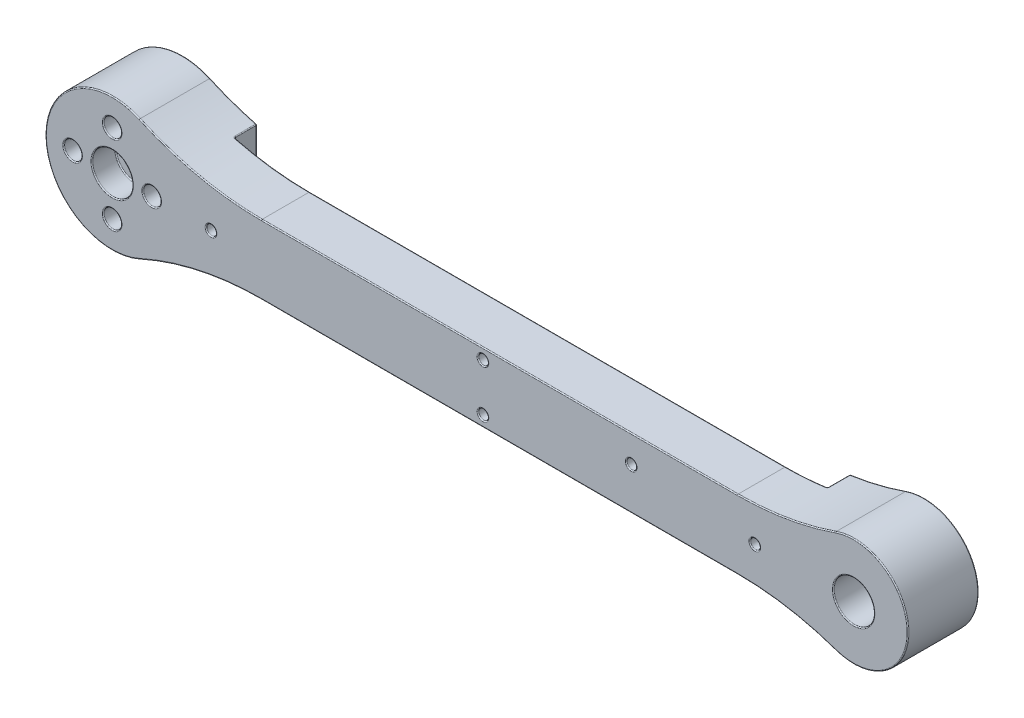
SolidWorks part; units mm, degrees
ref_plane "정면" through (0, 0, 0) normal (0, 0, 1) x (1, 0, 0)
ref_plane "윗면" through (0, 0, 0) normal (0, 1, 0) x (1, 0, 0)
ref_plane "우측면" through (0, 0, 0) normal (1, 0, 0) x (0, 0, -1)
sketch "스케치1" plane through (0, 0, 0) normal (0, 0, 1) x (1, 0, 0)
  line L0 (0, 11) -> (50, 11)
  line L1 (50, 11) -> (50, -11)
  line L2 (50, -11) -> (0, -11)
  line L3 (0, 0) -> (78.6227, 0) construction
  line L4 (8.4853, 7) -> (50, 7)
  line L5 (8.4853, -7) -> (50, -7)
  line L7 (0, -8) -> (0, 0) construction
  arc A0 (0, 11) -> (0, -11) centre (0, 0) ccw
  circle A1 centre (0, 0) radius 4.1
  circle A6 centre (0, 0) radius 11
  circle A7 centre (0, -8) radius 1.8
  circle A8 centre (-8, 0) radius 1.8
  circle A9 centre (0, 8) radius 1.8
  circle A10 centre (8, 0) radius 1.8
  point P15 (0, 0)
  point P26 (0, 0)
  dimension "D1" = 22
  dimension "D2" = 3.6
  dimension "D4" = 8.2
  dimension "D3" = 8
  dimension "D6" = 50
  dimension "D7" = 14
  dimension "D5" = 90
  dimension "D9" = 4
extrude "보스-돌출1" add sketch "스케치1" along normal blind 14.3 contours A6 A0 A10 A9 A8 A7 A1 | A6 L5 L1 L4 region at (4.5578, 9.6684, 0) region at (30.0954, 0, 0)
sketch "스케치3" plane through (0, 0, 0) normal (0, 0, -1) x (-1, 0, 0)
  circle A0 centre (0, 0) radius 4.1
  circle A1 centre (0, 0) radius 2.45
  circle M6 centre (0, 0) radius 4.1
  dimension "D1" = 8.2
  dimension "D2" = 4.9
extrude "보스-돌출2" add sketch "스케치3" against normal blind 9.5 contours A1 M6 region at (3.984, 0, 0)
sketch "스케치4" plane through (0, 0, 0) normal (0, 0, -1) x (-1, 0, 0)
  line L3 (-8.4853, 7) -> (-50, 7)
  line L4 (-50, 7) -> (-50, -7)
  line L5 (-50, -7) -> (-8.4853, -7)
  line L6 (-8.4853, 7) -> (-50, 7)
  line L7 (-50, 7) -> (-50, -7)
  line L8 (-50, -7) -> (-8.4853, -7)
  arc A0 (-3, 8) -> (3, 8) centre (0, 8) ccw
  circle A1 centre (-8, 0) radius 1.8
  circle A2 centre (-8, 0) radius 1.8
  circle A3 centre (0, 8) radius 1.8
  circle A4 centre (0, 8) radius 1.8
  circle A5 centre (8, 0) radius 1.8
  circle A6 centre (8, 0) radius 1.8
  circle A7 centre (0, -8) radius 1.8
  circle A8 centre (0, -8) radius 1.8
  circle A9 centre (0, 0) radius 2.45
  circle A10 centre (0, 0) radius 2.45
  arc A11 (8, 3) -> (8, -3) centre (8, 0) ccw
  circle A12 centre (-8, 0) radius 3
  arc A13 (3, -8) -> (-3, -8) centre (0, -8) ccw
  circle A14 centre (0, 8) radius 3
  circle A15 centre (8, 0) radius 3
  circle A16 centre (0, -8) radius 3
  arc A17 (-8.4853, -7) -> (-8.4853, 7) centre (0, 0) ccw
  circle A18 centre (0, 0) radius 13.5
  circle M9 centre (-8, 0) radius 1.8
  circle M10 centre (0, 8) radius 1.8
  circle M11 centre (8, 0) radius 1.8
  circle M12 centre (0, -8) radius 1.8
  dimension "D6" = 6
  dimension "D8" = 27
  dimension "D1" = 0
  dimension "D2" = 0
  dimension "D3" = 0
  dimension "D4" = 0
  dimension "D5" = 0
  dimension "D7" = 0
sketch "스케치6" plane through (0, 0, 0) normal (0, 0, -1) x (-1, 0, 0)
  line L0 (-50, 7) -> (-50, -7)
  line L1 (-50, -7) -> (-141.5147, -7)
  line L2 (-50, 7) -> (-141.5147, 7)
  circle A0 centre (-150, 0) radius 11
  circle A1 centre (-150, 0) radius 4.8
  circle A2 centre (-150, 0) radius 4.1
  line M22 (-50, 7) -> (-50, -7)
  dimension "D1" = 22
  dimension "D2" = 9.6
  dimension "D3" = 8.2
  dimension "D4" = 150
extrude "보스-돌출3" add sketch "스케치6" against normal up to surface (14.3 mm away) contours A0 L1 L2 M22 | A0 A1 | A1 A2 region at (94.9009, 0, 0) region at (139.9406, 3.6138, 0) region at (154.6642, 0, 0) up to face at (9.8, 0, 14.3)
sketch "스케치7" plane through (0, 0, 0) normal (0, 0, -1) x (-1, 0, 0)
  line L1 (-135, 7) -> (-15, 7)
  line L2 (-135, 7) -> (-135, -7)
  line L3 (-135, -7) -> (-15, -7)
  line L4 (-15, 7) -> (-15, -7)
  line L5 (-135, 7) -> (-15, -7) construction
  line L6 (-135, -7) -> (-15, 7) construction
  line L7 (-125.1, 2.6) -> (-24.9, 2.6)
  line L8 (-125.1, 2.6) -> (-125.1, -2.6)
  line L9 (-125.1, -2.6) -> (-24.9, -2.6)
  line L10 (-24.9, 2.6) -> (-24.9, -2.6)
  line L11 (-125.1, 2.6) -> (-24.9, -2.6) construction
  line L12 (-125.1, -2.6) -> (-24.9, 2.6) construction
  point P0 (-75, 0)
  point P5 (-75, 0)
  dimension "D1" = 75
  dimension "D2" = 14
  dimension "D3" = 120
  dimension "D4" = 100.2
  dimension "D5" = 5.2
extrude "컷-돌출6" cut sketch "스케치7" against normal blind 4.55 contours L2 L3 L4 L1
extrude "컷-돌출7" cut sketch "스케치7<3>" against normal blind 5.2 from surface contours L7 L10 L9 L8 starting at face at (75, 0, 4.55)
sketch "스케치7<3>" plane through (0, 0, 0) normal (0, 0, -1) x (-1, 0, 0) same geometry as "스케치7"
sketch "스케치8" plane through (0, 0, 4.55) normal (0, 0, -1) x (-1, 0, 0)
  line L0 (0, 0) -> (-78.6227, 0) construction
  line L1 (-135, 7) -> (-135, -7) construction
  line L2 (-15, 7) -> (-15, -7) construction
  line L4 (-50, 7) -> (-141.5147, 7) construction
  line L5 (-50, -7) -> (-141.5147, -7) construction
  circle A0 centre (-20, 0) radius 1
  circle A1 centre (-130, 0) radius 1
  circle A2 centre (-75, 4.8) radius 1
  circle A3 centre (-75, -4.8) radius 1
  dimension "D1" = 2
  dimension "D2" = 2
  dimension "D5" = 2
  dimension "D7" = 2
  dimension "D3" = 5
  dimension "D4" = 5
  dimension "D6" = 2.2
  dimension "D8" = 2.2
extrude "컷-돌출8" cut sketch "스케치8" against normal through all
sketch "스케치9" plane through (0, 0, 4.55) normal (0, 0, -1) x (-1, 0, 0)
  line L0 (-110, 7) -> (-110, -7) construction
  line L1 (-50, 7) -> (-141.5147, 7) construction
  line L2 (-50, -7) -> (-141.5147, -7) construction
  line L3 (-135, 7) -> (-15, 7) construction
  circle A0 centre (-105, 1.5) radius 1
  dimension "D1" = 2
  dimension "D2" = 40
  dimension "D3" = 5
  dimension "D4" = 5.5
extrude "컷-돌출9" cut sketch "스케치9" against normal through all
extrude "컷-돌출10" cut sketch "스케치6<4>" against normal blind 1.8 contours A1 A2 region at (154.6642, 0, 0)
sketch "스케치6<4>" plane through (0, 0, 0) normal (0, 0, -1) x (-1, 0, 0) same geometry as "스케치6"
fillet "필렛3" radius 60 2 edges at (141.5147, -7, 7.15) (141.5147, 7, 7.15)
sketch "스케치10" plane through (0, 0, 14.3) normal (0, 0, 1) x (1, 0, 0)
  circle A0 centre (0, 0) radius 13.5
  circle A1 centre (0, 0) radius 11
  dimension "D1" = 27
extrude "보스-돌출4" add sketch "스케치10" against normal up to surface (14.3 mm away) from surface up to face at (9.8, 0, 0) starting at face at (104, 1.5, 14.3)
fillet "필렛4" radius 60 2 edges at (11.5434, -7, 7.15) (11.5434, 7, 7.15)
extrude "컷-돌출11" cut sketch "스케치4" against normal blind 5 from surface contours A0 A14 M10 | A15 A11 M11 | A12 M9 | A13 A16 M12 region at (2.0613, -10.0613, 0) region at (-10.0613, -2.0613, 0) region at (-2.0613, 10.0613, 0) region at (10.9151, 0, 0) starting at face at (5.4777, 0, 0)
fillet "필렛5" radius 0.2 65 edges at (15, 8.9625, 2.275) (15, -8.9625, 2.275) (135, -7.6044, 2.275) (135, 7.6044, 2.275) (145.2, 0, 1.8) (145.9, 0, 1.8) (-4.1, 0, 9.5) (-2.45, 0, 9.5) (9.8, 0, 14.3) (1.8, 8, 14.3) (-6.2, 0, 14.3) (1.8, -8, 14.3) (4.1, 0, 14.3) (154.1, 0, 14.3) (74, -4.8, 14.3) (74, 4.8, 14.3) (129, 0, 14.3) (19, 0, 14.3) (104, 1.5, 14.3) (136.5755, 7.8511, 14.3) (161, 0, 14.3) (136.5755, -7.8511, 14.3) (78.3627, -7, 14.3) (17.6032, -8.3415, 14.3) (-13.5, 0, 14.3) (17.6032, 8.3415, 14.3) (78.3627, 7, 14.3) (-6.2, 0, 5) (-5, 0, 5) (1.8, -8, 5) (3, -8, 5) (1.8, 8, 5) (3, 8, 5) (9.8, 0, 5) (11, 0, 5) (3, 8, 0) (11, 0, 0) (-2.45, 0, 0) (10.2054, 10.4366, 0) (-13.5, 0, 0) (10.2054, -10.4366, 0) (15, 0, 0) (3, -8, 0) (-5, 0, 0) (22.547, 7.4926, 4.55) (15, 0, 4.55) (22.547, -7.4926, 4.55) (78.3627, -7, 4.55) (130.7634, -7.1513, 4.55) (135, 0, 4.55) (130.7634, 7.1513, 4.55) (78.3627, 7, 4.55) (125.1, 0, 4.55) (75, -2.6, 4.55) (24.9, 0, 4.55) (75, 2.6, 4.55) (74, -4.8, 4.55) (74, 4.8, 4.55) (129, 0, 4.55) (19, 0, 4.55) (140.7478, 8.7149, 0) (135, 0, 0) (140.7478, -8.7149, 0) (161, 0, 0) (145.2, 0, 0)
